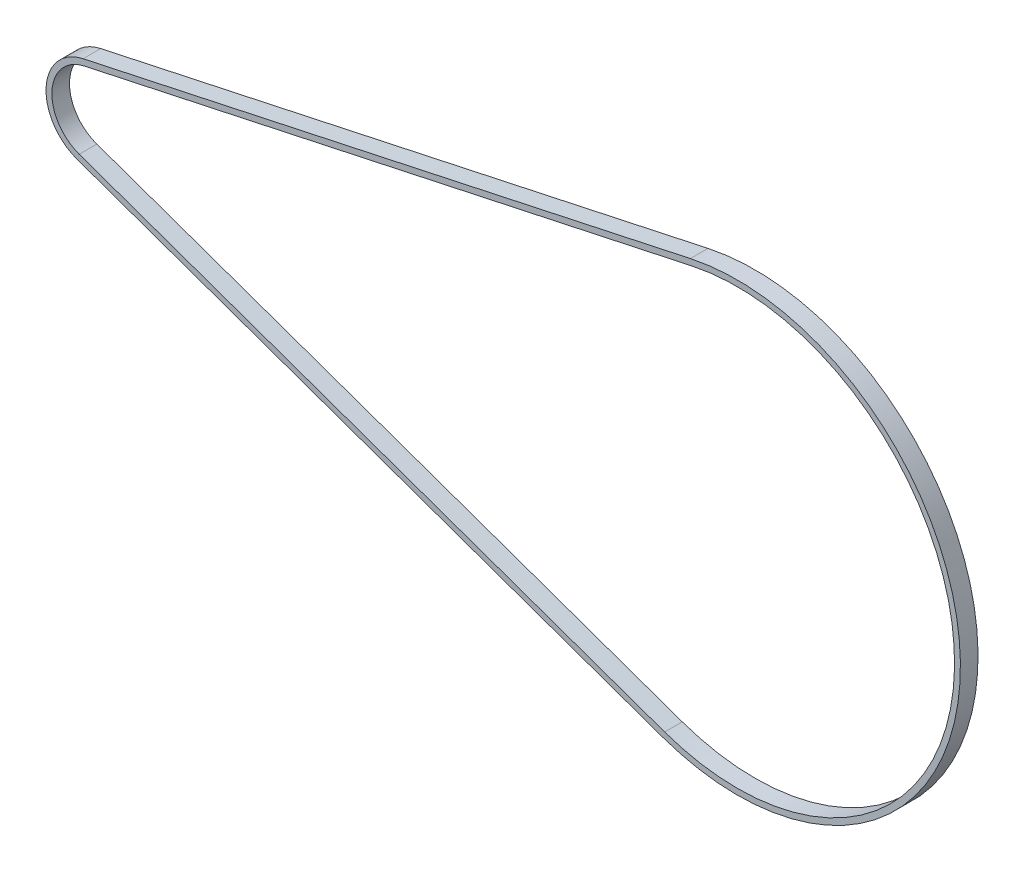
SolidWorks part; units mm, degrees
ref_plane "Front Plane" through (0, 0, 0) normal (0, 0, 1) x (1, 0, 0)
ref_plane "Top Plane" through (0, 0, 0) normal (0, 1, 0) x (1, 0, 0)
ref_plane "Right Plane" through (0, 0, 0) normal (1, 0, 0) x (0, 0, -1)
sketch "Sketch2" plane through (0, 0, 0) normal (0, 0, 1) x (1, 0, 0)
  line L0 (0, 0) -> (1, 0) construction
  line L1 (0, 0) -> (0, 1) construction
  line L2 (-3.7378, 17.3827) -> (258.9871, 73.8767)
  line L3 (247.3322, -106.5781) -> (-5.9428, -16.7574)
  arc A0 (-5.9428, -16.7574) -> (-3.7378, 17.3827) centre (0, 0) cw
  arc A1 (258.9871, 73.8767) -> (247.3322, -106.5781) centre (278.7441, -18.0031) cw
extrude "Extrude-Thin1" add sketch "Sketch2" along normal mid plane 7.62 thin thin type one direction wall 2.54
